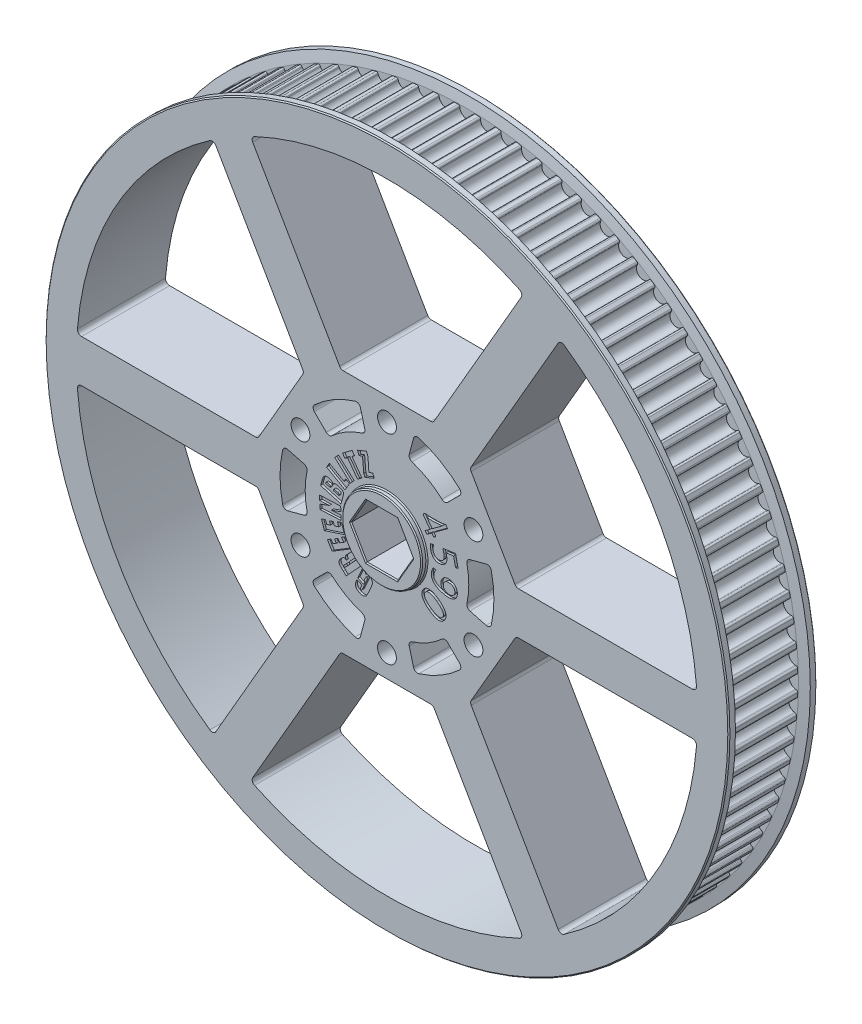
SolidWorks part; units mm, degrees
material "PETG"
ref_plane "Front Plane" through (0, 0, 0) normal (0, 0, 1) x (1, 0, 0)
ref_plane "Top Plane" through (0, 0, 0) normal (0, 1, 0) x (1, 0, 0)
ref_plane "Right Plane" through (0, 0, 0) normal (1, 0, 0) x (0, 0, -1)
sketch "Sketch2" plane through (0, 0, 0) normal (0, 0, 1) x (1, 0, 0)
  circle A0 centre (0, 0) radius 78.9906
  dimension "D1" = 157.9811
extrude "pulley" add sketch "Sketch2" along normal mid plane 17
sketch "tooth" plane through (0, 0, 0) normal (0, 0, 1) x (1, 0, 0)
  line L0 (0, 0) -> (0, 78.5906) construction
  line L1 (4.9975, 78.4315) -> (0, 78.5906) construction
  line L2 (4.9975, 78.4315) -> (0, 0) construction
  line L3 (-2.1327, 82.6262) -> (-1.6129, 78.3925)
  line L6 (2.1327, 82.6262) -> (1.6129, 78.3925)
  line L7 (-2.1327, 82.6262) -> (2.1327, 82.6262)
  arc A1 (-1.6129, 78.3925) -> (1.6129, 78.3925) centre (0, 78.5906) ccw
  arc A2 (0, 78.5906) -> (4.9975, 78.4315) centre (0, 0) cw construction
  circle A3 centre (4.9975, 78.4315) radius 1.625 construction
  dimension "D1" = 78.5906
  dimension "D2" = 3.25
  dimension "D3" = 5
  dimension "D4" = 3.646
  dimension "D5" = 14
extrude "cut tooth" cut sketch "tooth" against normal mid plane 17
fillet "blend tooth" radius 0.4 2 edges at (1.6841, 78.9726, 0) (-1.6841, 78.9726, 0)
pattern_circular "tooth pattern" count 100 over 360 about axis through (0, 0, 0) along (0, 0, 1) of "cut tooth", "blend tooth"
sketch "Sketch3" plane through (0, 0, 0) normal (0, 0, 1) x (1, 0, 0)
  circle A0 centre (0, 0) radius 81.5306
  circle A1 centre (0, 0) radius 78.9906 construction
  dimension "D1" = 2.54
extrude "sidewall" add sketch "Sketch3" along normal blind 2 from offset 8.5
mirror "mirror sidewall" about plane through (0, 0, 0) normal (0, 0, 1) of "sidewall"
chamfer "sidewall chamfer" distance 2.4 angle 10 2 edges at (81.5306, 0, 8.5) (81.5306, 0, -8.5)
sketch "Sketch5" plane through (0, 0, 0) normal (0, 0, 1) x (1, 0, 0)
  circle A0 centre (0, 0) radius 9.525
  dimension "D1" = 19.05
extrude "bearing spacer (Manual Suppress)" add sketch "Sketch5" along normal blind 11.77 and the other way blind 11.77
sketch "Sketch4" plane through (0, 0, 0) normal (0, 0, 1) x (1, 0, 0)
  line L1 (3.6882, 6.3881) -> (-3.6882, 6.3881)
  line L2 (-3.6882, 6.3881) -> (-7.3763, 0)
  line L3 (-7.3763, 0) -> (-3.6882, -6.3881)
  line L4 (-3.6882, -6.3881) -> (3.6882, -6.3881)
  line L5 (3.6882, -6.3881) -> (7.3763, 0)
  line L6 (7.3763, 0) -> (3.6882, 6.3881)
  circle A0 centre (0, 0) radius 6.3881 construction
  dimension "D1" = 12.7762
extrude "hex shaft" cut sketch "Sketch4" against normal mid plane 127
chamfer "chamfers" distance 0.254 angle 45 18 edges at (81.5306, 0, -10.5) (81.5306, 0, 10.5) (-9.525, 0, -10.5) (9.525, 0, 10.5) (9.525, 0, 11.77) (0, 6.3881, 11.77) (-5.5323, 3.194, 11.77) (-5.5323, -3.194, 11.77) (0, -6.3881, 11.77) (5.5323, -3.194, 11.77) (5.5323, 3.1941, 11.77) (9.525, 0, -11.77) (0, -6.3881, -11.77) (-5.5323, -3.194, -11.77) (-5.5323, 3.194, -11.77) (0, 6.3881, -11.77) (5.5323, 3.1941, -11.77) (5.5323, -3.194, -11.77)
sketch "SK-VersaCut" plane through (0, 0, 0) normal (0, 0, 1) x (1, 0, 0)
  line B0 (6.3387, 23.6565) -> (5.299, 19.7762)
  line B1 (14.4772, 14.4772) -> (17.3177, 17.3177)
  line B2 (23.6565, 6.3387) -> (19.7762, 5.299)
  line B3 (19.7762, -5.299) -> (23.6565, -6.3387)
  line B4 (17.3177, -17.3177) -> (14.4772, -14.4772)
  line B5 (5.299, -19.7762) -> (6.3387, -23.6565)
  line B6 (-6.3387, -23.6565) -> (-5.299, -19.7762)
  line B7 (-14.4772, -14.4772) -> (-17.3177, -17.3177)
  line B8 (-23.6565, -6.3387) -> (-19.7762, -5.299)
  line B9 (-19.7762, 5.299) -> (-23.6565, 6.3387)
  line B10 (-17.3177, 17.3177) -> (-14.4772, 14.4772)
  line B11 (-5.299, 19.7762) -> (-6.3387, 23.6565)
  circle B12 centre (0, 23.8125) radius 2.2479
  arc B13 (5.9535, 18.5765) -> (13.1109, 14.4442) centre (0, 0) cw
  arc B14 (7.5904, 24.3458) -> (17.2889, 18.7464) centre (0, 0) cw
  arc B15 (5.9535, 18.5765) -> (5.299, 19.7762) centre (6.2559, 19.5198) cw
  arc B16 (13.1109, 14.4442) -> (14.4772, 14.4772) centre (13.7767, 15.1777) ccw
  arc B17 (17.2889, 18.7464) -> (17.3177, 17.3177) centre (16.6173, 18.0182) cw
  arc B18 (7.5904, 24.3458) -> (6.3387, 23.6565) centre (7.2956, 23.4001) ccw
  circle B19 centre (20.6222, 11.9062) radius 2.2479
  arc B20 (19.0645, 4.1323) -> (19.0645, -4.1323) centre (0, 0) cw
  arc B21 (24.8793, 5.5994) -> (24.8793, -5.5994) centre (0, 0) cw
  arc B22 (19.0645, 4.1323) -> (19.7762, 5.299) centre (20.0326, 4.3422) cw
  arc B23 (19.0645, -4.1323) -> (19.7762, -5.299) centre (20.0326, -4.3422) ccw
  arc B24 (24.8793, -5.5994) -> (23.6565, -6.3387) centre (23.9129, -5.3819) cw
  arc B25 (24.8793, 5.5994) -> (23.6565, 6.3387) centre (23.9129, 5.3819) ccw
  circle B26 centre (20.6222, -11.9063) radius 2.2479
  arc B27 (13.1109, -14.4442) -> (5.9535, -18.5765) centre (0, 0) cw
  arc B28 (17.2889, -18.7464) -> (7.5904, -24.3458) centre (0, 0) cw
  arc B29 (13.1109, -14.4442) -> (14.4772, -14.4772) centre (13.7767, -15.1777) cw
  arc B30 (5.9535, -18.5765) -> (5.299, -19.7762) centre (6.2559, -19.5198) ccw
  arc B31 (7.5904, -24.3458) -> (6.3387, -23.6565) centre (7.2956, -23.4001) cw
  arc B32 (17.2889, -18.7464) -> (17.3177, -17.3177) centre (16.6173, -18.0182) ccw
  circle B33 centre (0, -23.8125) radius 2.2479
  arc B34 (-5.9535, -18.5765) -> (-13.1109, -14.4442) centre (0, 0) cw
  arc B35 (-7.5904, -24.3458) -> (-17.2889, -18.7464) centre (0, 0) cw
  arc B36 (-5.9535, -18.5765) -> (-5.299, -19.7762) centre (-6.2559, -19.5198) cw
  arc B37 (-13.1109, -14.4442) -> (-14.4772, -14.4772) centre (-13.7767, -15.1777) ccw
  arc B38 (-17.2889, -18.7464) -> (-17.3177, -17.3177) centre (-16.6173, -18.0182) cw
  arc B39 (-7.5904, -24.3458) -> (-6.3387, -23.6565) centre (-7.2956, -23.4001) ccw
  circle B40 centre (-20.6222, -11.9063) radius 2.2479
  arc B41 (-19.0645, -4.1323) -> (-19.0645, 4.1323) centre (0, 0) cw
  arc B42 (-24.8793, -5.5994) -> (-24.8793, 5.5994) centre (0, 0) cw
  arc B43 (-19.0645, -4.1323) -> (-19.7762, -5.299) centre (-20.0326, -4.3422) cw
  arc B44 (-19.0645, 4.1323) -> (-19.7762, 5.299) centre (-20.0326, 4.3422) ccw
  arc B45 (-24.8793, 5.5994) -> (-23.6565, 6.3387) centre (-23.9129, 5.3819) cw
  arc B46 (-24.8793, -5.5994) -> (-23.6565, -6.3387) centre (-23.9129, -5.3819) ccw
  circle B47 centre (-20.6222, 11.9063) radius 2.2479
  arc B48 (-13.1109, 14.4442) -> (-5.9535, 18.5765) centre (0, 0) cw
  arc B49 (-17.2889, 18.7464) -> (-7.5904, 24.3458) centre (0, 0) cw
  arc B50 (-13.1109, 14.4442) -> (-14.4772, 14.4772) centre (-13.7767, 15.1777) cw
  arc B51 (-5.9535, 18.5765) -> (-5.299, 19.7762) centre (-6.2559, 19.5198) ccw
  arc B52 (-7.5904, 24.3458) -> (-6.3387, 23.6565) centre (-7.2956, 23.4001) cw
  arc B53 (-17.2889, 18.7464) -> (-17.3177, 17.3177) centre (-16.6173, 18.0182) ccw
sketch_block_instance "VersaKey-1"
sketch_block "Block1" parameters "D1"=47.625, "D2"=4.4958, "D3"=19.5072, "D4"=25.5016, "D6"=0.9906, "D5"=30
extrude "VersaKeys (Manual Suppress)" cut sketch "SK-VersaCut" against normal through all both and the other way through all
sketch "Lightening Holes" plane through (0, 0, 0) normal (0, 0, 1) x (1, 0, 0)
  line L0 (-32.0143, 65.6104) -> (-11.2845, 29.7053)
  line L1 (11.2845, 29.7053) -> (32.0143, 65.6104)
  line L14 (0, 0) -> (-3.6662, 6.35) construction
  line L15 (0, 0) -> (0, 6.35) construction
  line L24 (0, 0) -> (3.6662, 6.35) construction
  line L25 (0, 6.35) -> (-3.6662, 6.35) construction
  line L26 (0, 6.35) -> (3.6662, 6.35) construction
  line L27 (-10.4266, 29.21) -> (10.4266, 29.21)
  line L28 (0, 6.35) -> (0, 29.21) construction
  line L29 (40.8131, 60.5304) -> (20.0833, 24.6253)
  line L30 (20.0833, 23.6347) -> (30.5099, 5.5753)
  line L31 (31.3678, 5.08) -> (72.8274, 5.08)
  line L32 (72.8274, -5.08) -> (31.3678, -5.08)
  line L33 (30.5099, -5.5753) -> (20.0833, -23.6347)
  line L34 (20.0833, -24.6253) -> (40.8131, -60.5304)
  line L35 (32.0143, -65.6104) -> (11.2845, -29.7053)
  line L36 (10.4266, -29.21) -> (-10.4266, -29.21)
  line L37 (-11.2845, -29.7053) -> (-32.0143, -65.6104)
  line L38 (-40.8131, -60.5304) -> (-20.0833, -24.6253)
  line L39 (-20.0833, -23.6347) -> (-30.5099, -5.5753)
  line L40 (-31.3678, -5.08) -> (-72.8274, -5.08)
  line L41 (-72.8274, 5.08) -> (-31.3678, 5.08)
  line L42 (-30.5099, 5.5753) -> (-20.0833, 23.6347)
  line L43 (-20.0833, 24.6253) -> (-40.8131, 60.5304)
  arc A3 (-31.5787, 67.0017) -> (31.5787, 67.0017) centre (0, 0) cw
  arc A4 (-10.4266, 29.21) -> (-11.2845, 29.7053) centre (-10.4266, 30.2006) cw
  arc A5 (10.4266, 29.21) -> (11.2845, 29.7053) centre (10.4266, 30.2006) ccw
  arc A6 (31.5787, 67.0017) -> (32.0143, 65.6104) centre (31.1564, 66.1057) cw
  arc A7 (-31.5787, 67.0017) -> (-32.0143, 65.6104) centre (-31.1564, 66.1057) ccw
  arc A72 (42.2358, 60.8488) -> (73.8146, 6.1529) centre (0, 0) cw
  arc A73 (42.2358, 60.8488) -> (40.8131, 60.5304) centre (41.671, 60.0351) ccw
  arc A74 (20.0833, 23.6347) -> (20.0833, 24.6253) centre (20.9412, 24.13) cw
  arc A75 (73.8146, 6.1529) -> (72.8274, 5.08) centre (72.8274, 6.0706) cw
  arc A76 (73.8146, -6.1529) -> (42.2358, -60.8488) centre (0, 0) cw
  arc A77 (73.8146, -6.1529) -> (72.8274, -5.08) centre (72.8274, -6.0706) ccw
  arc A78 (30.5099, -5.5753) -> (31.3678, -5.08) centre (31.3678, -6.0706) cw
  arc A79 (42.2358, -60.8488) -> (40.8131, -60.5304) centre (41.671, -60.0351) cw
  arc A80 (31.5787, -67.0017) -> (-31.5787, -67.0017) centre (0, 0) cw
  arc A81 (31.5787, -67.0017) -> (32.0143, -65.6104) centre (31.1564, -66.1057) ccw
  arc A82 (10.4266, -29.21) -> (11.2845, -29.7053) centre (10.4266, -30.2006) cw
  arc A83 (-31.5787, -67.0017) -> (-32.0143, -65.6104) centre (-31.1564, -66.1057) cw
  arc A84 (-42.2358, -60.8488) -> (-73.8146, -6.1529) centre (0, 0) cw
  arc A85 (-42.2358, -60.8488) -> (-40.8131, -60.5304) centre (-41.671, -60.0351) ccw
  arc A86 (-20.0833, -23.6347) -> (-20.0833, -24.6253) centre (-20.9412, -24.13) cw
  arc A87 (-73.8146, -6.1529) -> (-72.8274, -5.08) centre (-72.8274, -6.0706) cw
  arc A88 (-73.8146, 6.1529) -> (-42.2358, 60.8488) centre (0, 0) cw
  arc A89 (-73.8146, 6.1529) -> (-72.8274, 5.08) centre (-72.8274, 6.0706) ccw
  arc A90 (-30.5099, 5.5753) -> (-31.3678, 5.08) centre (-31.3678, 6.0706) cw
  arc A91 (-42.2358, 60.8488) -> (-40.8131, 60.5304) centre (-41.671, 60.0351) cw
  arc A92 (30.5099, 5.5753) -> (31.3678, 5.08) centre (31.3678, 6.0706) ccw
  arc A93 (20.0833, -23.6347) -> (20.0833, -24.6253) centre (20.9412, -24.13) ccw
  arc A94 (-10.4266, -29.21) -> (-11.2845, -29.7053) centre (-10.4266, -30.2006) ccw
  arc A95 (-30.5099, -5.5753) -> (-31.3678, -5.08) centre (-31.3678, -6.0706) ccw
  arc A96 (-20.0833, 23.6347) -> (-20.0833, 24.6253) centre (-20.9412, 24.13) ccw
  point P72 (0, 0)
  point P77 (0, 0)
  point P87 (0, 0)
  dimension "D4" = 74.0706
  dimension "D6" = 0.9906
  dimension "D5" = 5.08
  dimension "D7" = 60
  dimension "D1" = 6.35
  dimension "D3" = 22.86
  dimension "D2" = 6
extrude "Weight Reduction (Manual Suppress)" cut sketch "Lightening Holes" against normal through all both and the other way through all
sketch "Sketch6" plane through (0, 0, 0) normal (0, 0, 1) x (1, 0, 0)
  line L0 (0, 11.1154) -> (0, 0) construction
  line L1 (0, 0) -> (0, -11.1154) construction
  arc A1 (0, 11.1154) -> (0, -11.1154) centre (0, 0) cw construction
  arc A2 (0, 11.1154) -> (0, -11.1154) centre (0, 0) ccw construction
  text T0 "4590\r\n" font "Ebrima" height in points 24
  text T1 "GREENBLITZ\r\n" font "Impact" height in points 18
extrude "Team nuber" cut sketch "Sketch6" along normal blind 2.54 from offset 9.992
equation "\"INPUT_pulley_teeth\"= 100"
equation "\"pulley_c2c\"= 5mm"
equation "\"pulley_teeth_deg\"= 360 / \"INPUT_pulley_teeth\""
equation "\"pulley_radius\"= ( \"pulley_c2c\" / ( 2 * cos ( \"iso_half_angle\" ) ) ) - 1mm"
equation "\"iso_half_angle\"= ( 180 - \"pulley_teeth_deg\" ) / 2"
equation "\"D1@tooth\" = \"pulley_radius\""
equation "\"pulley_tooth_dia\"= 3.25mm"
equation "\"D3@tooth\"=\"pulley_c2c\""
equation "\"D2@tooth\"=\"pulley_tooth_dia\""
equation "\"D1@Sketch2\"=2* \"pulley_radius\"+\"pulley_tooth_offset\""
equation "\"pulley_tooth_offset\"= .8mm"
equation "\"D1@tooth pattern\" = \"INPUT_pulley_teeth\""
equation "\"INPUT_pulley_belt_9_or_15_(unitless)\"= 15"
equation "\"D1@pulley\"=\"pulley_width\""
equation "\"D19@sidewall\" =  ( \"pulley_width\" / 2 ) "
equation "\"D1@sidewall\"=\"pulley_sidewall_thick\""
equation "\"pulley_width\"= IIF ( \"INPUT_pulley_belt_9_or_15_(unitless)\" = 9 , 11mm , 17mm )"
equation "\"D1@cut tooth\"=\"pulley_width\""
equation "\"D1@sidewall chamfer\" = 2.4mm"
equation "\"D4@Lightening Holes\"=\"pulley_radius\"-\"pulley_tooth_dia\"-.05"
equation "\"D1@bearing spacer (Manual Suppress)\" = 0.05 +  ( \"pulley_width\" / 2 )  + \"pulley_sidewall_thick\""
equation "\"D2@bearing spacer (Manual Suppress)\" = 0.05 +  ( \"pulley_width\" / 2 )  + \"pulley_sidewall_thick\""
equation "\"pulley_sidewall_thick\"= 2mm"
equation "\"D1@Team nuber\" = \"pulley_width\""
equation "\"D19@Team nuber\" =  ( \"pulley_width\" / 2 )  + \"pulley_sidewall_thick\" - 0.02"
equation "\"rad_len\" = \"INPUT_pulley_teeth\" * \"pulley_c2c\""
